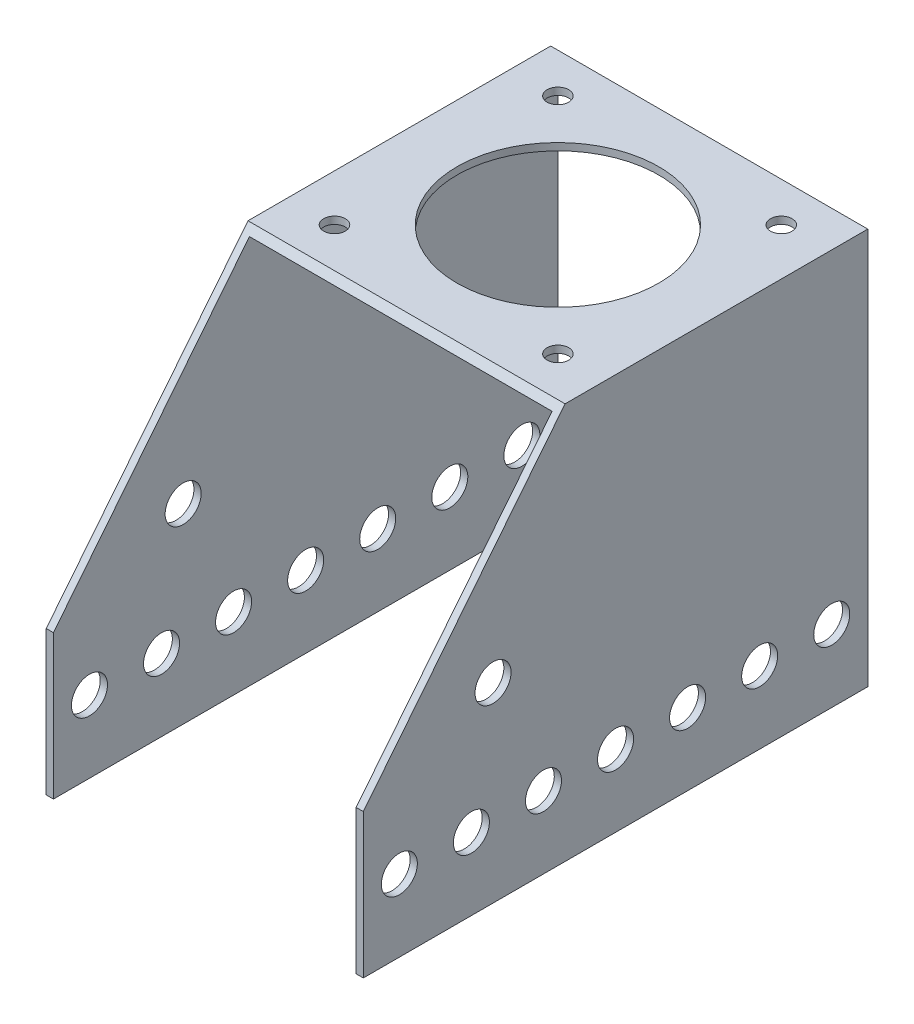
SolidWorks part; units mm, degrees
ref_plane "Front Plane" through (0, 0, 0) normal (0, 0, 1) x (1, 0, 0)
ref_plane "Top Plane" through (0, 0, 0) normal (0, 1, 0) x (1, 0, 0)
ref_plane "Right Plane" through (0, 0, 0) normal (1, 0, 0) x (0, 0, -1)
sketch "Sketch1" plane through (0, 0, 0) normal (0, 0, 1) x (1, 0, 0)
  line L0 (-21, -27.5) -> (-21, 26.5)
  line L1 (-22, -27.5) -> (-21, -27.5)
  line L2 (-22, -27.5) -> (-22, 27.5)
  line L3 (-22, 27.5) -> (22, 27.5)
  line L4 (22, -27.5) -> (22, 27.5)
  line L5 (-22, -27.5) -> (22, 27.5) construction
  line L6 (-22, 27.5) -> (22, -27.5) construction
  line L7 (-21, 26.5) -> (21, 26.5)
  line L8 (21, 26.5) -> (21, -27.5)
  line L9 (21, -27.5) -> (22, -27.5)
  point P0 (0, 0)
  point P8 (21.5, -27.5)
  dimension "D1" = 54
  dimension "D2" = 1
  dimension "D3" = 42
  dimension "D4" = 1
extrude "Boss-Extrude1" add sketch "Sketch1" along normal blind 70
sketch "Sketch2" plane through (0, 27.5, 0) normal (0, 1, 0) x (1, 0, 0)
  line L1 (-22, -21) -> (22, -21) construction
  line L2 (-22, -70) -> (-22, 0) construction
  line L4 (0, -21) -> (15.5, -36.5) construction
  line L7 (22, -70) -> (22, 0) construction
  line L8 (22, 0) -> (-22, 0) construction
  circle A0 centre (15.5, -36.5) radius 1.5
  circle A4 centre (0, -21) radius 14
  circle A5 centre (-15.5, -36.5) radius 1.5
  circle A6 centre (-15.5, -5.5) radius 1.5
  circle A7 centre (15.5, -5.5) radius 1.5
  point P19 (0, -21)
  point P24 (0, -21)
  dimension "D2" = 3
  dimension "D4" = 28
  dimension "D3" = 21
  dimension "D5" = 45
  dimension "D6" = 21.9203
  dimension "D1" = 4
extrude "Cut-Extrude1" cut sketch "Sketch2" against normal through all
sketch "Sketch5" plane through (-22, 0, 0) normal (-1, 0, 0) x (0, 0, 1)
  line L0 (70, -7.5) -> (42, 27.5)
  line L1 (70, 27.5) -> (70, -27.5) construction
  line L2 (70, 27.5) -> (0, 27.5) construction
  line L3 (42, 27.5) -> (70, 27.5)
  line L4 (70, 27.5) -> (70, -7.5)
  line L5 (70, -7.5) -> (70, -27.5) construction
  line L6 (5, -17.5) -> (0, -17.5) construction
  line L7 (0, 27.5) -> (0, -27.5) construction
  line L8 (65, -17.5) -> (70, -17.5) construction
  line L9 (5, -17.5) -> (15, -17.5) construction
  circle A0 centre (5, -17.5) radius 2.5
  circle A1 centre (15, -17.5) radius 2.5
  circle A2 centre (25, -17.5) radius 2.5
  circle A3 centre (35, -17.5) radius 2.5
  circle A4 centre (45, -17.5) radius 2.5
  circle A5 centre (55, -17.5) radius 2.5
  circle A6 centre (65, -17.5) radius 2.5
  circle A7 centre (52, -1.0078) radius 2.5
  point P12 (70, -17.5)
  point P14 (52, 5.2163)
  dimension "D6" = 5
  dimension "D7" = 10
  dimension "D1" = 42
  dimension "D2" = 20
  dimension "D4" = 10
  dimension "D5" = 10
  dimension "D3" = 7
extrude "Cut-Extrude3" cut sketch "Sketch5" against normal through all
